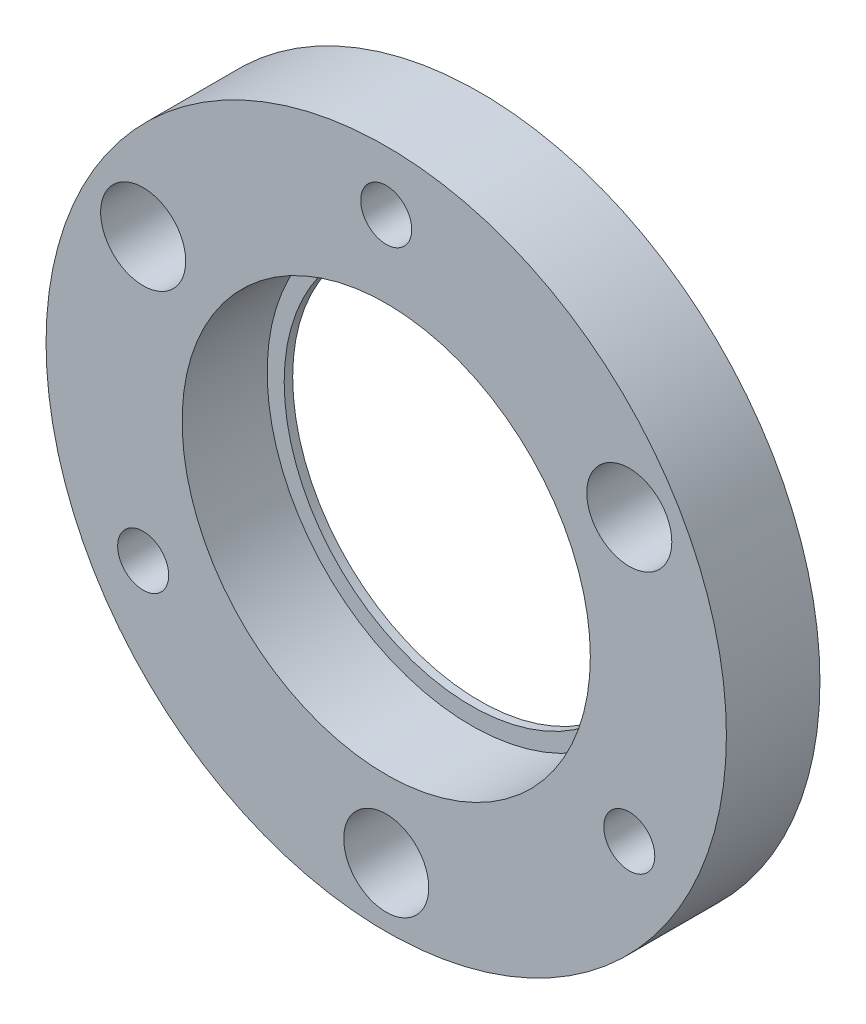
SolidWorks part; units mm, degrees
ref_plane "Front Plane" through (0, 0, 0) normal (0, 0, 1) x (1, 0, 0)
ref_plane "Top Plane" through (0, 0, 0) normal (0, 1, 0) x (1, 0, 0)
ref_plane "Right Plane" through (0, 0, 0) normal (1, 0, 0) x (0, 0, -1)
sketch "Sketch1" plane through (0, 0, 0) normal (0, 0, 1) x (1, 0, 0)
  circle A0 centre (0, 0) radius 12
  circle A1 centre (0, 0) radius 11
  circle A2 centre (0, 0) radius 20
  circle A3 centre (0, 0) radius 16.5 construction
  circle A4 centre (0, 16.5) radius 1.5
  circle A5 centre (14.2894, -8.25) radius 1.5
  circle A6 centre (-14.2894, -8.25) radius 1.5
  circle A7 centre (0, -16.5) radius 2.5
  circle A8 centre (-14.2894, 8.25) radius 2.5
  circle A9 centre (14.2894, 8.25) radius 2.5
  point P14 (0, 0)
  point P21 (0, 0)
  dimension "D1" = 24
  dimension "D2" = 22
  dimension "D3" = 40
  dimension "D4" = 33
  dimension "D5" = 3
  dimension "D7" = 5
  dimension "D6" = 3
  dimension "D8" = 3
extrude "Boss-Extrude1" add sketch "Sketch1" along normal blind 5 contours A2 A9 A8 A7 A6 A5 A4 A0 region at (-19.4343, 0, 0)
extrude "Boss-Extrude2" add sketch "Sketch1<3>" against normal blind 0.5 contours A0 A1 | A2 A9 A8 A7 A6 A5 A4 A0 region at (-11.6606, 0, 0) region at (-19.4343, 0, 0)
sketch "Sketch1<3>" plane through (0, 0, 0) normal (0, 0, 1) x (1, 0, 0) same geometry as "Sketch1"
